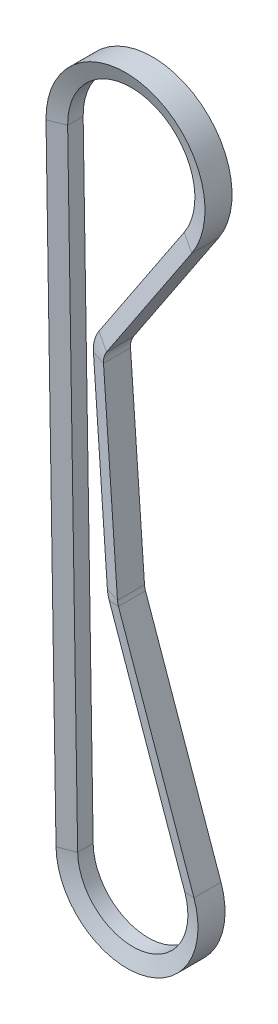
SolidWorks part; units mm, degrees
ref_plane "Front Plane" through (0, 0, 0) normal (0, 0, 1) x (1, 0, 0)
ref_plane "Top Plane" through (0, 0, 0) normal (0, 1, 0) x (1, 0, 0)
ref_plane "Right Plane" through (0, 0, 0) normal (1, 0, 0) x (0, 0, -1)
sketch "Sketch2" plane through (0, 0, 0) normal (0, 0, 1) x (1, 0, 0)
  line L0 (0, 0) -> (1, 0) construction
  line L1 (0, 0) -> (0, 1) construction
  line L12 (-24.9968, -0.4008) -> (-28.5237, 219.5505)
  line L14 (22.7886, 204.4954) -> (-7.2305, 159.3509)
  line L15 (-8.2772, 155.3891) -> (-3.3639, 85.5617)
  line L16 (-3.0195, 83.8997) -> (23.5827, 8.2981)
  arc A4 (-28.5237, 219.5505) -> (22.7886, 204.4954) centre (-0.5273, 219.9994) cw
  arc A7 (23.5827, 8.2981) -> (-24.9968, -0.4008) centre (0, 0) cw
  arc A8 (-7.2305, 159.3509) -> (-8.2772, 155.3891) centre (-1.9428, 155.8348) ccw
  arc A9 (-3.3639, 85.5617) -> (-3.0195, 83.8997) centre (2.9705, 86.0074) ccw
ref_plane "Plane4" through (23.5827, 8.2981, 0) normal (0.3319, -0.9433, 0) x (-0.9433, -0.3319, 0)
sketch "Sketch3" plane through (23.5827, 8.2981, 0) normal (0.3319, -0.9433, 0) x (-0.9433, -0.3319, 0)
  line L0 (0, -4.7625) -> (0, 4.7625)
  line L1 (0, -4.7625) -> (5.588, -2.7286)
  line L2 (5.588, -2.7286) -> (5.588, 2.7286)
  line L3 (5.588, 2.7286) -> (0, 4.7625)
  line L4 (0, 0) -> (5.588, 0) construction
  dimension "D1" = 9.525
  dimension "D2" = 5.588
  dimension "D3" = 40
sweep "Sweep1" add profiles "Sketch3" path "Sketch2"
